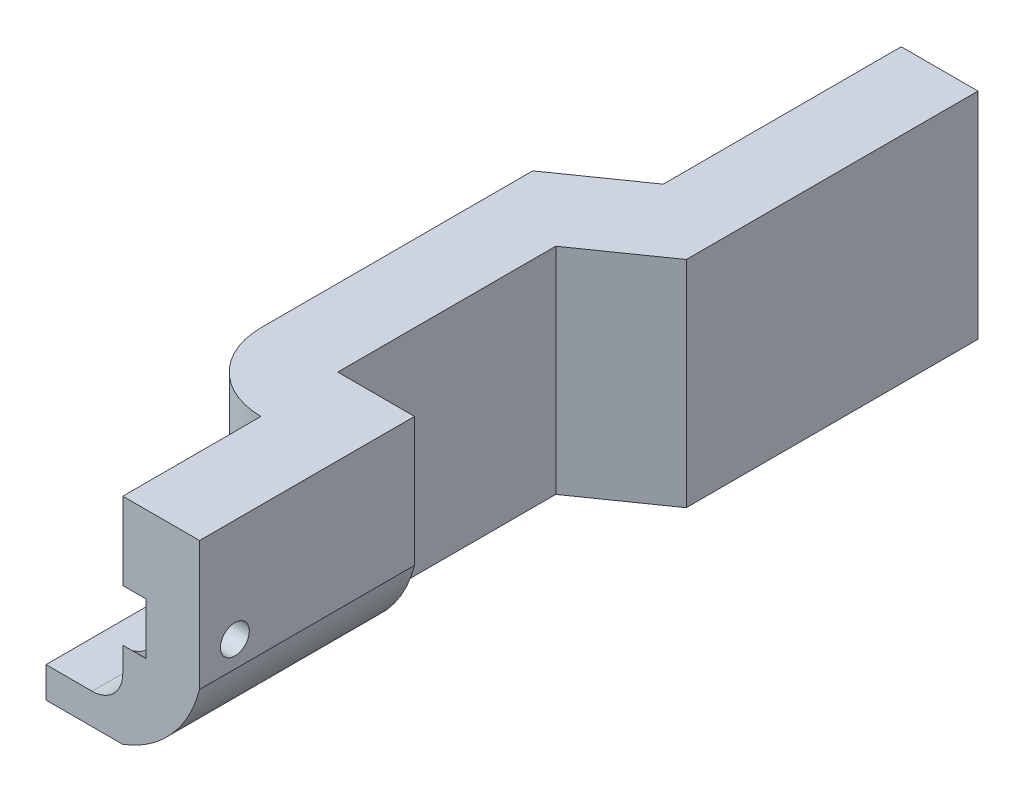
SolidWorks part; units mm, degrees
ref_plane "Front Plane" through (0, 0, 0) normal (0, 0, 1) x (1, 0, 0)
ref_plane "Top Plane" through (0, 0, 0) normal (0, 1, 0) x (1, 0, 0)
ref_plane "Right Plane" through (0, 0, 0) normal (1, 0, 0) x (0, 0, -1)
sketch "Croquis1" plane through (0, 0, 0) normal (0, 1, 0) x (1, 0, 0)
  line L0 (0, 0) -> (5, 0)
  line L1 (0, 0) -> (0, 22.7)
  line L2 (5, 0) -> (5, 19.2)
  line L5 (5, 26.2) -> (0, 22.7)
  line L8 (10, 22.7) -> (5, 19.2)
  line L9 (5, 26.2) -> (5, 41.7)
  line L10 (5, 41.7) -> (10, 41.7)
  line L11 (10, 41.7) -> (10, 22.7)
  dimension "D1" = 5
  dimension "D2" = 22.7
  dimension "D3" = 19.2
  dimension "D4" = 15.5
extrude "Saliente-Extruir1" add sketch "Croquis1" along normal blind 14
sketch "Croquis2" plane through (0, 0, 0) normal (0, 0, 1) x (1, 0, 0)
  line L2 (0, 0) -> (0, 2)
  line L3 (0, 14) -> (0, 0) construction
  line L4 (5, 14) -> (10, 14)
  line L5 (10, 14) -> (10, 0)
  line L6 (10, 0) -> (0, 0)
  line L7 (0, 2) -> (5, 2)
  line L8 (5, 14) -> (5, 0) construction
  line L9 (5, 14) -> (5, 2)
extrude "Saliente-Extruir3" add sketch "Croquis2" along normal blind 9 and the other way blind 5
sketch "Croquis5" plane through (0, 0, 0) normal (-1, 0, 0) x (0, 0, 1)
  line L2 (9, 14) -> (9, 2) construction
  circle A0 centre (6.7, 7.28) radius 2.85
  dimension "D1" = 5.7
  dimension "D2" = 2.3
extrude "Cortar-Extruir3" cut sketch "Croquis5" against normal blind 6.5
sketch "Croquis6" plane through (0, 0, 9) normal (0, 0, 1) x (1, 0, 0)
  line L0 (0, 0) -> (10, 0) construction
  line L1 (10, 0) -> (10, 14) construction
  line L2 (5, 0) -> (10, 0)
  line L3 (10, 0) -> (10, 5.597)
  arc A1 (5, 0) -> (10, 5.597) centre (2.1441, 7.5831) ccw
  point P10 (0, 0)
extrude "Cortar-Extruir4" cut sketch "Croquis6" against normal blind 21
sketch "Croquis7" plane through (0, 0, 0) normal (0, -1, 0) x (1, 0, 0)
  line L0 (0, 9) -> (5, 9) construction
  line L4 (10, -41.7) -> (5, -41.7) construction
  circle A0 centre (7.5, -37) radius 1
  circle A2 centre (2.5, -5.1) radius 1
  dimension "D1" = 2
  dimension "D2" = 2
  dimension "D4" = 4.7
  dimension "D3" = 14.1
extrude "Cortar-Extruir5" cut sketch "Croquis7" against normal blind 5
sketch "Croquis8" plane through (6.5, 0, 0) normal (-1, 0, 0) x (0, 0, 1)
  circle A0 centre (6.7, 7.28) radius 0.94
  dimension "D1" = 1.88
extrude "Cortar-Extruir6" cut sketch "Croquis8" against normal through all
fillet "Redondeo2" radius 5 1 edges at (0, 8, 0)
fillet "Redondeo3" radius 2 1 edges at (5, 2, 4.5)
